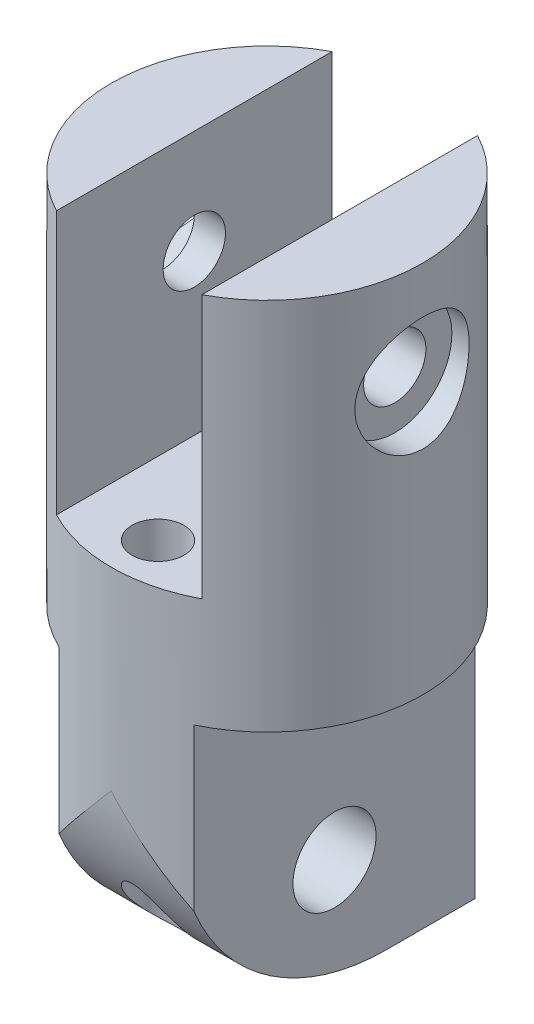
SolidWorks part; units mm, degrees
ref_plane "Front Plane" through (0, 0, 0) normal (0, 0, 1) x (1, 0, 0)
ref_plane "Top Plane" through (0, 0, 0) normal (0, 1, 0) x (1, 0, 0)
ref_plane "Right Plane" through (0, 0, 0) normal (1, 0, 0) x (0, 0, -1)
sketch "Sketch1" plane through (0, 0, 0) normal (0, 0, 1) x (1, 0, 0)
  line L1 (-3.25, 7) -> (3.25, 7)
  line L2 (-3.25, 7) -> (-3.25, -7)
  line L3 (-3.25, -7) -> (3.25, -7)
  line L4 (3.25, 7) -> (3.25, -7)
  line L5 (-3.25, 7) -> (3.25, -7) construction
  line L6 (-3.25, -7) -> (3.25, 7) construction
  point P0 (0, 0)
  dimension "D1" = 6.5
  dimension "D2" = 14
extrude "Boss-Extrude1" add sketch "Sketch1" along normal blind 15
fillet "Fillet1" radius 10 1 edges at (0, -7, 15)
sketch "Sketch2" plane through (3.25, 0, 0) normal (1, 0, 0) x (0, 0, -1)
  line L0 (-7.5, 7) -> (-7.5, -6.6825) construction
  line L1 (-15, 7) -> (0, 7) construction
  arc A0 (-15, 3) -> (-5, -7) centre (-5, 3) ccw construction
  circle A1 centre (-7.5, -2) radius 2
  dimension "D1" = 4
  dimension "D2" = 4.6825
extrude "Cut-Extrude1" cut sketch "Sketch2" against normal through all
sketch "Sketch4" plane through (0, 7, 0) normal (0, 1, 0) x (1, 0, 0)
  line L0 (0, 0) -> (0, -15) construction
  line L1 (3.25, 0) -> (-3.25, 0) construction
  line L2 (3.25, -15) -> (-3.25, -15) construction
  circle A0 centre (0, -7.5) radius 7.5
  dimension "D1" = 15
extrude "Boss-Extrude2" add sketch "Sketch4" along normal blind 18
sketch "Sketch6" plane through (0, 0, 0) normal (0, 0, -1) x (-1, 0, 0)
  line L0 (7.5, 25) -> (-7.5, 25) construction
  line L1 (3.5, 25) -> (-3.5, 25)
  line L2 (3.5, 25) -> (3.5, 12.32)
  line L3 (3.5, 12.32) -> (-3.5, 12.32)
  line L4 (-3.5, 25) -> (-3.5, 12.32)
  point P4 (0, 12.32)
  dimension "D1" = 7
  dimension "D2" = 12.68
extrude "Cut-Extrude2" cut sketch "Sketch6" against normal through all
sketch "Sketch7" plane through (0, 7, 0) normal (0, 1, 0) x (1, 0, 0)
  line L2 (-3.25, -14.2593) -> (-3.25, -15)
  line L3 (-3.25, -15) -> (0, -15)
  line L4 (-3.25, -14.2593) -> (-3.25, -15)
  line L5 (-3.25, -15) -> (0, -15)
  line L6 (0, -15) -> (3.25, -15)
  line L7 (3.25, -15) -> (3.25, -14.2593)
  line L8 (0, -15) -> (3.25, -15)
  line L9 (3.25, -15) -> (3.25, -14.2593)
  line L10 (0, 0) -> (-3.25, 0)
  line L11 (-3.25, 0) -> (-3.25, -0.7407)
  line L12 (0, 0) -> (-3.25, 0)
  line L13 (-3.25, 0) -> (-3.25, -0.7407)
  line L14 (3.25, -0.7407) -> (3.25, 0)
  line L15 (3.25, 0) -> (0, 0)
  line L16 (3.25, -0.7407) -> (3.25, 0)
  line L17 (3.25, 0) -> (0, 0)
  arc A1 (-3.25, -14.2593) -> (0, -15) centre (0, -7.5) ccw
  arc A2 (-3.25, -14.2593) -> (0, -15) centre (0, -7.5) ccw
  arc A3 (0, -15) -> (3.25, -14.2593) centre (0, -7.5) ccw
  arc A4 (0, -15) -> (3.25, -14.2593) centre (0, -7.5) ccw
  arc A5 (0, 0) -> (-3.25, -0.7407) centre (0, -7.5) ccw
  arc A6 (0, 0) -> (-3.25, -0.7407) centre (0, -7.5) ccw
  arc A7 (3.25, -0.7407) -> (0, 0) centre (0, -7.5) ccw
  arc A8 (3.25, -0.7407) -> (0, 0) centre (0, -7.5) ccw
  arc M13 (0, -15) -> (-3.25, -14.2593) centre (0, -7.5) cw
  line M14 (-3.25, -14.2593) -> (-3.25, -15)
  line M15 (-3.25, -15) -> (0, -15)
  dimension "D1" = 0
  dimension "D2" = 0
  dimension "D3" = 0
  dimension "D4" = 0
extrude "Cut-Extrude3" cut sketch "Sketch7" against normal through all contours A6 L12 L13 | A8 L16 L17 | M15 M13 M14 | A4 L8 L9 region at (-2.4457, 7, 14.7798) region at (2.4457, 7, 14.7798) region at (-2.4457, 7, 0.2202) region at (2.4457, 7, 0.2202)
sketch "Sketch8" plane through (-3.5, 0, 0) normal (1, 0, 0) x (0, 0, -1)
  line L0 (-7.5, 12.32) -> (-7.5, 25) construction
  line L1 (-14.1332, 12.32) -> (-0.8668, 12.32) construction
  line L2 (-0.8668, 25) -> (-14.1332, 25) construction
  circle A0 centre (-7.5, 20) radius 1.5
  dimension "D2" = 3
  dimension "D1" = 5
extrude "Cut-Extrude4" cut sketch "Sketch8" against normal mid plane 42
ref_plane "Plane1" through (6.15, 0, 0) normal (-1, 0, 0) x (0, 0, 1)
sketch "Sketch9" plane through (6.15, 0, 0) normal (-1, 0, 0) x (0, 0, 1)
  circle A0 centre (7.5, 20) radius 2.75
  dimension "D1" = 5.5
extrude "Cut-Extrude5" cut sketch "Sketch9" against normal blind 10
ref_plane "Plane2" through (-5, 0, 0) normal (1, 0, 0) x (0, 0, -1)
sketch "Sketch10" plane through (-5, 0, 0) normal (1, 0, 0) x (0, 0, -1)
  line L0 (-7.5, 23.7528) -> (-7.5, 20) construction
  line L1 (-7.5, 23.7528) -> (-10.75, 21.8764)
  line L2 (-10.75, 21.8764) -> (-10.75, 18.1236)
  line L3 (-10.75, 18.1236) -> (-7.5, 16.2472)
  line L4 (-7.5, 16.2472) -> (-4.25, 18.1236)
  line L5 (-4.25, 18.1236) -> (-4.25, 21.8764)
  line L6 (-4.25, 21.8764) -> (-7.5, 23.7528)
  circle A0 centre (-7.5, 20) radius 3.25 construction
  dimension "D1" = 6.5
extrude "Cut-Extrude6" cut sketch "Sketch10" against normal blind 10
sketch "Sketch11" plane through (0, -7, 0) normal (0, -1, 0) x (1, 0, 0)
  line L0 (3.25, 5) -> (-3.25, 5) construction
  circle A1 centre (0, 3) radius 1.25
  circle A3 centre (0, 12.7488) radius 1.25
  dimension "D1" = 2
extrude "Cut-Extrude7" cut sketch "Sketch11" against normal blind 24 contours A3 | A1 region at (0, -7, 3) region at (0, -7, 12.7488)
